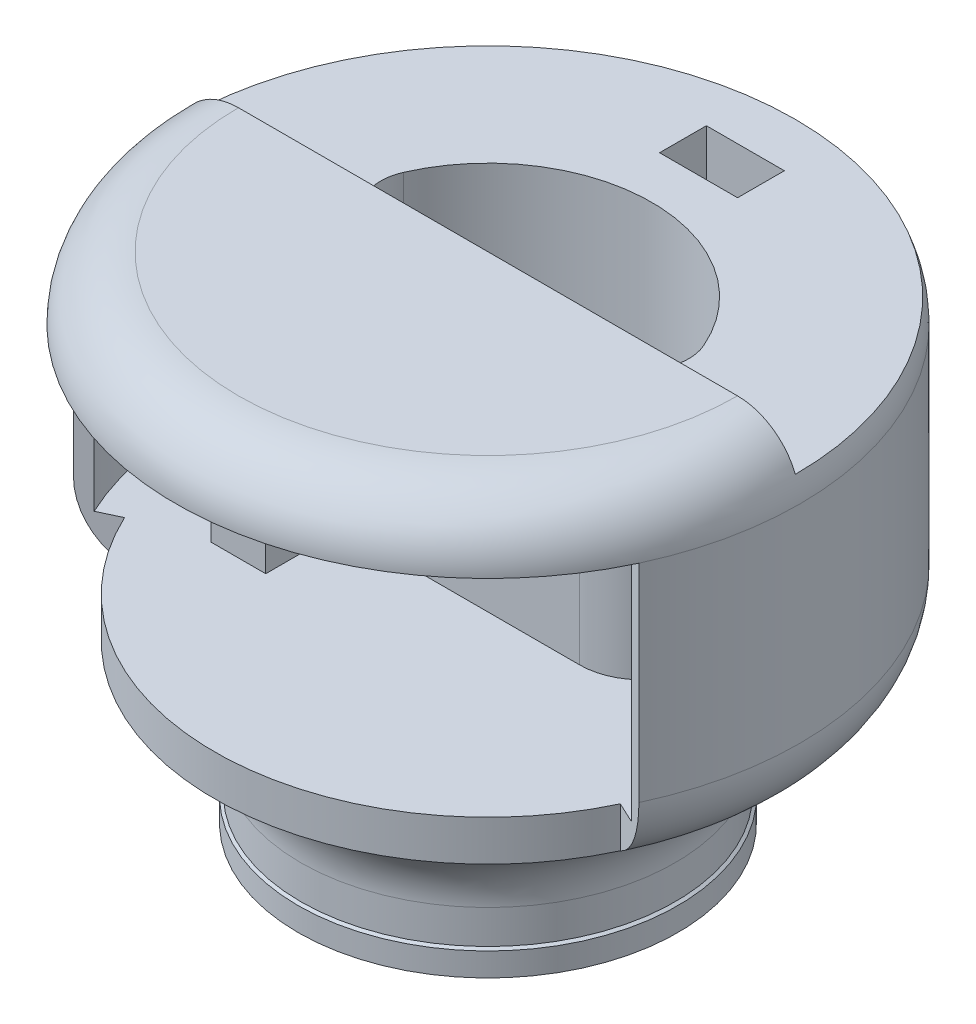
SolidWorks part; units mm, degrees
ref_plane "Front Plane" through (0, 0, 0) normal (0, 0, 1) x (1, 0, 0)
ref_plane "Top Plane" through (0, 0, 0) normal (0, 1, 0) x (1, 0, 0)
ref_plane "Right Plane" through (0, 0, 0) normal (1, 0, 0) x (0, 0, -1)
sketch "Sketch1" plane through (0, 0, 0) normal (0, 0, 1) x (1, 0, 0)
  line L0 (0, 0) -> (0, 90.2242) construction
  line L28 (0, 63.4279) -> (32, 63.4279)
  line L29 (40, 55.4279) -> (40, 28.8468)
  line L30 (22.5, 0) -> (24.35, 0)
  line L31 (24.35, 0) -> (24.35, 3)
  line L32 (24.35, 3) -> (24, 3.25)
  line L33 (24, 3.25) -> (24, 7.5811)
  line L34 (28.5399, 15.9588) -> (35.4601, 20.4691)
  line L35 (0, 13) -> (22, 13)
  line L36 (22.5, 12.5) -> (22.5, 0)
  line L37 (0, 13) -> (0, 63.4279)
  arc A0 (22, 13) -> (22.5, 12.5) centre (22, 12.5) cw
  arc A1 (24, 7.5811) -> (28.5399, 15.9588) centre (34, 7.5811) cw
  arc A2 (35.4601, 20.4691) -> (40, 28.8468) centre (30, 28.8468) ccw
  arc A3 (32, 63.4279) -> (40, 55.4279) centre (32, 55.4279) cw
  point P11 (22.9, 63.4279)
  point P18 (22.5, 13)
  point P21 (24, 13)
  point P24 (40, 23.4279)
  point P27 (40, 63.4279)
  point P28 (28.5604, 23.4279)
  point P31 (22.5, 17)
  dimension "D8" = 9.75
  dimension "D9" = 0.5
  dimension "D4" = 1.85
  dimension "D1" = 22.5
  dimension "D10" = 10
  dimension "D11" = 10
  dimension "D12" = 8
  dimension "D2" = 40
  dimension "D3" = 40
  dimension "D5" = 1.5
  dimension "D6" = 3
  dimension "D7" = 13
revolve "Revolve1" add sketch "Sketch1" angle 360 about L0
ref_plane "Plane1" through (0, 13, 0) normal (0, -1, 0) x (-1, 0, 0)
sketch "Sketch18" plane through (0, 0, 0) normal (0, 0, 1) x (1, 0, 0)
  line L0 (0, 0) -> (0, 101.5813) construction
  line L1 (-24.35, 0) -> (24.35, 0) construction
sketch "Sketch3" plane through (0, 0, 0) normal (0, 0, 1) x (1, 0, 0)
  point P0 (1.2404, 19.1989)
ref_point "Point1"
ref_plane "Plane2" through (0, 0, 22.9) normal (0, 0, 1) x (1, 0, 0)
ref_plane "Plane3" through (0, 0, 40) normal (0, 0, 1) x (1, 0, 0)
ref_plane "Plane4" through (0, 55.4279, 0) normal (0, 1, 0) x (1, 0, 0)
sketch "Sketch9" plane through (0, 55.4279, 0) normal (0, 1, 0) x (1, 0, 0)
  circle A7 centre (0, 0) radius 38
  circle A8 centre (0, 0) radius 40 construction
  circle A9 centre (0, 0) radius 23
  dimension "D1" = 2
  dimension "D2" = 46
ref_plane "Plane5" through (0, 13, 0) normal (0, -1, 0) x (-1, 0, 0)
sketch "Sketch11" plane through (0, 13, 0) normal (0, -1, 0) x (-1, 0, 0)
  line L0 (-21, 0) -> (21, 0)
  arc A1 (-21, 0) -> (21, 0) centre (0, 0) cw
  dimension "D1" = 42
extrude "Cut-Extrude3" cut sketch "Sketch11" against normal blind 60
ref_plane "Plane6" through (0, 0, -40) normal (0, 0, -1) x (-1, 0, 0)
extrude "Cut-Extrude5" cut sketch "Sketch9" against normal blind 30 and the other way blind 2
sketch "Sketch19" plane through (0, 0, 0) normal (1, 0, 0) x (0, 0, -1)
  line L0 (-47.0647, 55.4279) -> (-35.0647, 55.4279)
  line L1 (31.2976, 55.4279) -> (-31.2976, 55.4279) construction
  line L2 (-35.0647, 55.4279) -> (-35.0647, 18.9279)
  line L3 (-35.0647, 18.9279) -> (-47.0647, 18.9279)
  line L4 (-47.0647, 18.9279) -> (-47.0647, 55.4279)
  dimension "D1" = 12
  dimension "D2" = 36.5
revolve "Cut-Revolve2" cut sketch "Sketch19" angle 65 about L0 other way angle 65
ref_plane "Plane7" through (0, 0, 22.5) normal (0, 0, -1) x (-1, 0, 0)
sketch "Sketch21" plane through (0, 0, 22.5) normal (0, 0, -1) x (-1, 0, 0)
  line L0 (0, 0) -> (0, 101.5813) construction
  line L1 (-1.625, 4) -> (1.625, 4)
  line L2 (-1.625, 4) -> (-1.625, 0)
  line L3 (-1.625, 0) -> (1.625, 0)
  line L4 (1.625, 4) -> (1.625, 0)
  line L5 (-1.625, 4) -> (1.625, 0) construction
  line L6 (-1.625, 0) -> (1.625, 4) construction
  line L7 (-22.5, 0) -> (22.5, 0) construction
  point P0 (0, 2)
  dimension "D1" = 4
  dimension "D2" = 3.25
extrude "Boss-Extrude3" add sketch "Sketch21" along normal blind 1.35
pattern_circular "CirPattern1" count 5 over 360 about axis through (0, 0, 0) along (0, -1, 0) of "Boss-Extrude3"
ref_plane "Plane8" through (0, 20.4691, 0) normal (0, 1, 0) x (1, 0, 0)
sketch "Sketch22" plane through (0, 63.4279, 0) normal (0, 1, 0) x (1, 0, 0)
  line L0 (-40, 0) -> (40, 0)
  arc A0 (-40, 0) -> (40, 0) centre (0, 0) cw
  arc A1 (36.2523, -16.9047) -> (-36.2523, -16.9047) centre (0, 0) ccw construction
extrude "Cut-Extrude9" cut sketch "Sketch22" against normal blind 5
sketch "Sketch23" plane through (0, 0, -40) normal (0, 0, -1) x (-1, 0, 0)
  line L0 (0, 0) -> (0, 101.5813) construction
  line L1 (31.2976, 55.4279) -> (-31.2976, 55.4279) construction
  circle A0 centre (0, 42.1379) radius 10.5
  dimension "D1" = 21
  dimension "D2" = 13.29
extrude "Cut-Extrude10" cut sketch "Sketch23" against normal blind 10
sketch "Sketch24" plane through (0, 58.4279, 0) normal (0, 1, 0) x (1, 0, 0)
  line L1 (-7.5, 34) -> (7.5, 34)
  line L2 (-7.5, 34) -> (-7.5, 26)
  line L3 (-7.5, 26) -> (7.5, 26)
  line L4 (7.5, 34) -> (7.5, 26)
  line L5 (-7.5, 34) -> (7.5, 26) construction
  line L6 (-7.5, 26) -> (7.5, 34) construction
  arc A0 (39.4162, 0) -> (-39.4162, 0) centre (0, 0) ccw construction
  point P0 (0, 30)
  dimension "D1" = 30
  dimension "D2" = 8
  dimension "D3" = 15
extrude "Boss-Extrude4" add sketch "Sketch24" against normal blind 8
sketch "Sketch26" plane through (0, 58.4279, 0) normal (0, 1, 0) x (1, 0, 0)
  line L1 (-5, 33) -> (5, 33)
  line L2 (-5, 33) -> (-5, 27)
  line L3 (-5, 27) -> (5, 27)
  line L4 (5, 33) -> (5, 27)
  line L5 (-5, 33) -> (5, 27) construction
  line L6 (-5, 27) -> (5, 33) construction
  arc A0 (39.4162, 0) -> (-39.4162, 0) centre (0, 0) ccw construction
  point P0 (0, 30)
  dimension "D1" = 30
  dimension "D2" = 6
  dimension "D3" = 10
extrude "Cut-Extrude11" cut sketch "Sketch26" against normal blind 10
sketch "Sketch27" plane through (7.5, 0, 0) normal (1, 0, 0) x (0, 0, -1)
  line L0 (34, 50.4279) -> (34, 57.4279) construction
  line L1 (28, 56.4279) -> (32, 56.4279)
  line L2 (28, 56.4279) -> (28, 51.4279)
  line L3 (28, 51.4279) -> (32, 51.4279)
  line L4 (32, 56.4279) -> (32, 51.4279)
  line L5 (28, 56.4279) -> (32, 51.4279) construction
  line L6 (28, 51.4279) -> (32, 56.4279) construction
  line L7 (26, 50.4279) -> (26, 57.4279) construction
  line L8 (26, 50.4279) -> (34, 50.4279) construction
  point P0 (30, 53.9279)
  dimension "D1" = 8
  dimension "D2" = 3.5
  dimension "D3" = 5
  dimension "D4" = 4
extrude "Cut-Extrude12" cut sketch "Sketch27" against normal blind 5
ref_plane "Plane10" through (0, 58.4279, 0) normal (0, 1, 0) x (1, 0, 0)
sketch "Sketch28" plane through (0, 55.4279, 0) normal (0, 1, 0) x (1, 0, 0)
  line L0 (-22.9129, -2) -> (22.9129, -2)
  arc A0 (-22.9129, -2) -> (22.9129, -2) centre (0, 0) ccw
  dimension "D1" = 46
  dimension "D2" = 2
extrude "Cut-Extrude14" cut sketch "Sketch28" against normal blind 30 and the other way blind 2
sketch "Sketch29" plane through (0, 0, 0) normal (0, 0, -1) x (-1, 0, 0)
  line L0 (0, 0) -> (0, 101.5813) construction
  line L1 (32, 63.4279) -> (-32, 63.4279) construction
  circle A0 centre (-30.4162, 60.9279) radius 1
  circle A1 centre (30.4162, 60.9279) radius 1
  circle A2 centre (0, 60.9279) radius 1
  dimension "D1" = 2
  dimension "D2" = 2
  dimension "D3" = 2
  dimension "D4" = 2.5
  dimension "D5" = 2.5
  dimension "D6" = 2.5
  dimension "D7" = 9
  dimension "D8" = 9
extrude "Cut-Extrude15" cut sketch "Sketch29" against normal blind 15
fillet "Fillet1" radius 6 2 edges at (-21, 35.7139, 0) (21, 35.7139, 0)
fillet "Fillet2" radius 8 2 edges at (22.9129, 41.4279, 2) (-22.9129, 41.4279, 2)
sketch "Sketch31" plane through (0, 58.4279, 0) normal (0, 1, 0) x (1, 0, 0)
  line L1 (-3.5, -27) -> (3.5, -27)
  line L2 (-3.5, -27) -> (-3.5, -32)
  line L3 (-3.5, -32) -> (3.5, -32)
  line L4 (3.5, -27) -> (3.5, -32)
  line L5 (-3.5, -27) -> (3.5, -32) construction
  line L6 (-3.5, -32) -> (3.5, -27) construction
  point P0 (0, -29.5)
  dimension "D1" = 7
  dimension "D2" = 5
  dimension "D3" = 29.5
extrude "Boss-Extrude7" add sketch "Sketch31" against normal blind 13
sketch "Sketch32" plane through (3.5, 0, 0) normal (1, 0, 0) x (0, 0, -1)
  line L1 (-27, 45.4279) -> (-27, 57.4279) construction
  line L4 (-32, 45.4279) -> (-27, 45.4279) construction
  circle A0 centre (-29.5, 48.4279) radius 1.25
  dimension "D1" = 2.5
  dimension "D2" = 3
  dimension "D3" = 2.5
extrude "Cut-Extrude16" cut sketch "Sketch32" against normal blind 7.5
